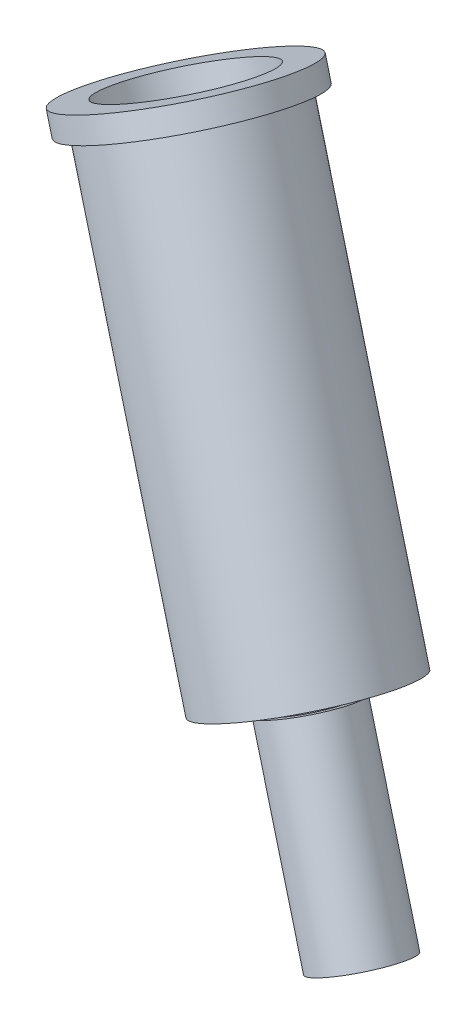
SolidWorks part; units mm, degrees
other "Markup1"
sketch "Sketch7" plane through (-206.0284, 201.4318, -3.7457) normal (-0.8382, 0.5448, -0.0267) x (0.4541, 0.7241, 0.5191)
ref_plane "Front Plane" through (0, 0, 0) normal (0, 0, 1) x (1, 0, 0)
ref_plane "Top Plane" through (0, 0, 0) normal (0, 1, 0) x (1, 0, 0)
ref_plane "Right Plane" through (0, 0, 0) normal (1, 0, 0) x (0, 0, -1)
sketch "Sketch1" plane through (-129.2035, 253.122, -50.2713) normal (-0.4477, 0.8771, -0.1742) x (0.8839, 0.4046, -0.2345)
  circle A0 centre (-31.0857, -28.5191) radius 11.43
  dimension "D1" = 22.86
extrude "Boss-Extrude1" add sketch "Sketch1" along normal blind 2.54 contours A0
sketch "Sketch2" plane through (-129.2035, 253.122, -50.2713) normal (0.4477, -0.8771, 0.1742) x (-0.8839, -0.4046, 0.2345)
  circle A0 centre (31.0857, -28.5191) radius 9.9949
  dimension "D1" = 19.9898
extrude "Boss-Extrude2" add sketch "Sketch2" along normal blind 48.26
sketch "Sketch3" plane through (-107.5981, 210.7951, -41.865) normal (0.4477, -0.8771, 0.1742) x (-0.8839, -0.4046, 0.2345)
  line L0 (33.4658, -38.4046) -> (28.7055, -18.6336) construction
  circle A0 centre (31.0857, -28.5191) radius 3.81
  dimension "D1" = 7.62
extrude "Boss-Extrude3" add sketch "Sketch3" along normal blind 1.016 contours A0
sketch "Sketch4" plane through (-107.1433, 209.904, -41.688) normal (0.4477, -0.8771, 0.1742) x (-0.8839, -0.4046, 0.2345)
  line L0 (39.2348, -26.557) -> (22.9365, -30.4812) construction
  circle A0 centre (31.0857, -28.5191) radius 4.7625
  dimension "D1" = 9.525
extrude "Boss-Extrude4" add sketch "Sketch4" along normal blind 21.336 contours A0
sketch "Sketch5" plane through (-130.3406, 255.3497, -50.7138) normal (-0.4477, 0.8771, -0.1742) x (0.8839, 0.4046, -0.2345)
  line L0 (-33.4658, -38.4046) -> (-28.7055, -18.6336) construction
  circle A0 centre (-31.0857, -28.5191) radius 3.175
  dimension "D1" = 6.35
extrude "Cut-Extrude1" cut sketch "Sketch5" against normal through all
sketch "Sketch6" plane through (-130.3406, 255.3497, -50.7138) normal (-0.4477, 0.8771, -0.1742) x (0.8839, 0.4046, -0.2345)
  circle A0 centre (-31.0857, -28.5191) radius 7.9375
  dimension "D1" = 15.875
extrude "Cut-Extrude2" cut sketch "Sketch6" against normal blind 22.86
